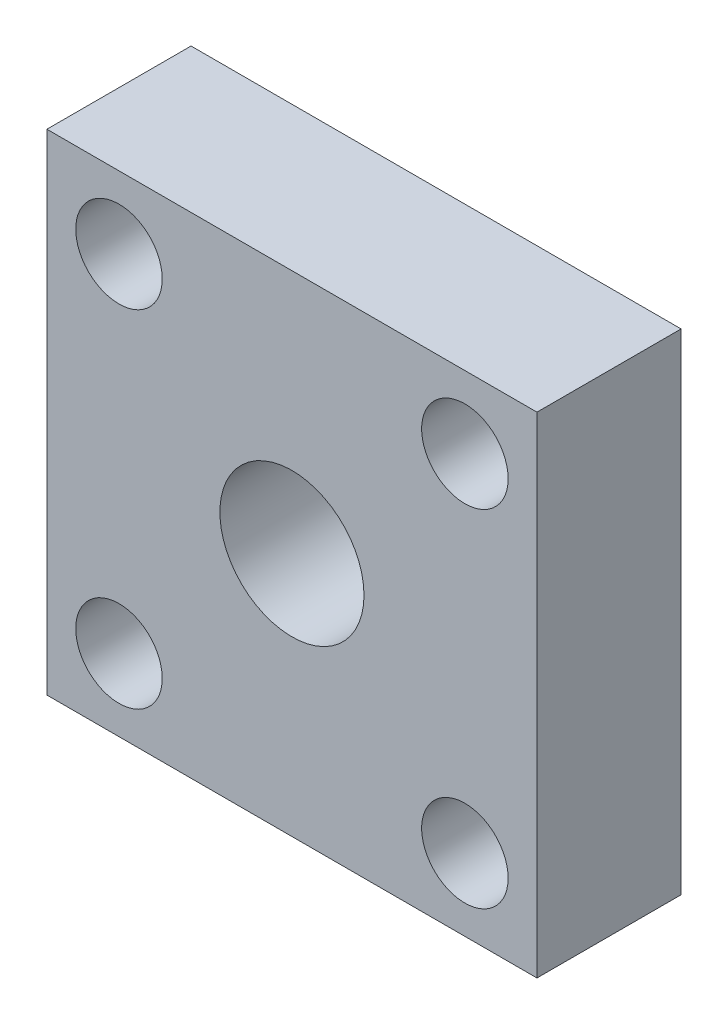
SolidWorks part; units mm, degrees
ref_plane "Front Plane" through (0, 0, 0) normal (0, 0, 1) x (1, 0, 0)
ref_plane "Top Plane" through (0, 0, 0) normal (0, 1, 0) x (1, 0, 0)
ref_plane "Right Plane" through (0, 0, 0) normal (1, 0, 0) x (0, 0, -1)
sketch "Sketch1" plane through (0, 0, 0) normal (0, 0, 1) x (1, 0, 0)
  line L1 (-18.4444, 12.1111) -> (15.5556, 12.1111)
  line L2 (-18.4444, 12.1111) -> (-18.4444, -21.8889)
  line L3 (-18.4444, -21.8889) -> (15.5556, -21.8889)
  line L4 (15.5556, 12.1111) -> (15.5556, -21.8889)
  circle A0 centre (-1.4444, -4.8889) radius 5
  dimension "D3" = 17
  dimension "D1" = 34
  dimension "D2" = 34
  dimension "D4" = 17
extrude "Boss-Extrude1" add sketch "Sketch1" along normal blind 10
sketch "Sketch2" plane through (0, 0, 10) normal (0, 0, 1) x (1, 0, 0)
  line L0 (-18.4444, 12.1111) -> (-18.4444, -21.8889) construction
  line L1 (15.5556, 12.1111) -> (-18.4444, 12.1111) construction
  circle A0 centre (-13.4444, 7.1111) radius 3
  dimension "D1" = 5
  dimension "D2" = 5
extrude "Cut-Extrude1" cut sketch "Sketch2" against normal blind 5
pattern_linear "LPattern1" count 2 spacing 24 along (1, 0, 0) count 2 spacing 24 along (0, -1, 0) of "Cut-Extrude1"
